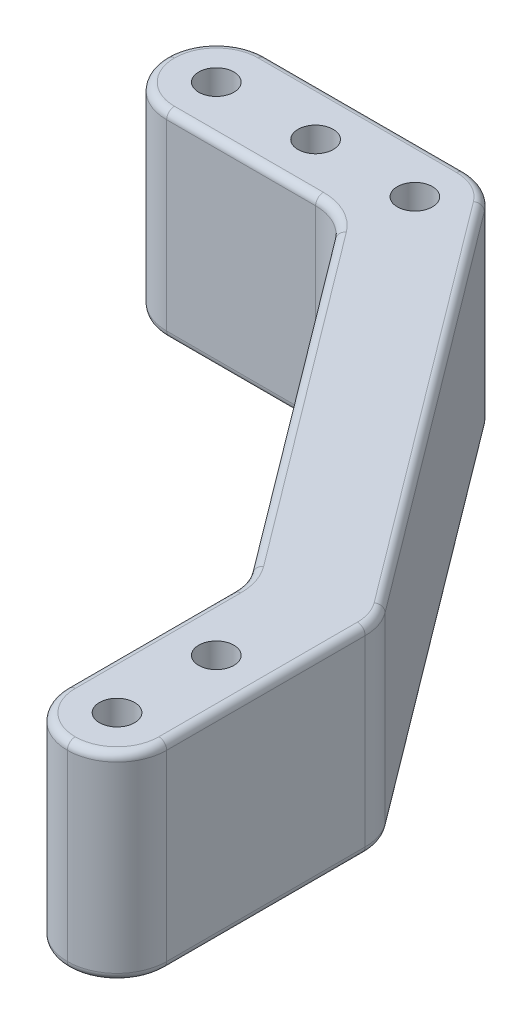
SolidWorks part; units mm, degrees
ref_plane "Front Plane" through (0, 0, 0) normal (0, 0, 1) x (1, 0, 0)
ref_plane "Top Plane" through (0, 0, 0) normal (0, 1, 0) x (1, 0, 0)
ref_plane "Right Plane" through (0, 0, 0) normal (1, 0, 0) x (0, 0, -1)
sketch "Sketch1" plane through (0, 0, 0) normal (0, 1, 0) x (1, 0, 0)
  line L0 (0, 0) -> (25.4, 0) construction
  line L1 (25.4, 0) -> (63.5, -50.8) construction
  line L2 (63.5, -50.8) -> (63.5, -76.2) construction
  line L3 (-6.35, 6.35) -> (-6.35, -6.35)
  line L4 (-6.35, -6.35) -> (22.225, -6.35)
  line L5 (22.225, -6.35) -> (57.15, -52.9167)
  line L6 (57.15, -52.9167) -> (57.15, -82.55)
  line L7 (57.15, -82.55) -> (69.85, -82.55)
  line L8 (69.85, -82.55) -> (69.85, -48.6833)
  line L9 (69.85, -48.6833) -> (28.575, 6.35)
  line L10 (28.575, 6.35) -> (-6.35, 6.35)
  circle A0 centre (0, 0) radius 2.25
  circle A1 centre (63.5, -76.2) radius 2.25
  circle A2 centre (63.5, -63.5) radius 2.25
  circle A3 centre (12.7, 0) radius 2.25
  circle A4 centre (25.4, 0) radius 2.25
  dimension "D10" = 4.5
  dimension "D1" = 25.4
  dimension "D2" = 25.4
  dimension "D3" = 50.8
  dimension "D4" = 38.1
  dimension "D5" = 12.7
  dimension "D6" = 12.7
  dimension "D7" = 6.35
  dimension "D8" = 6.35
  dimension "D9" = 12.7
  dimension "D11" = 3
extrude "Boss-Extrude1" add sketch "Sketch1" along normal blind 25.4
fillet "Fillet1" radius 6.35 8 edges at (28.575, 12.7, -6.35) (22.225, 12.7, 6.35) (69.85, 12.7, 48.6833) (57.15, 12.7, 52.9167) (69.85, 12.7, 82.55) (57.15, 12.7, 82.55) (-6.35, 12.7, -6.35) (-6.35, 12.7, 6.35)
fillet "Fillet2" radius 1 28 edges at (-4.4901, 0, 4.4901) (-4.4901, 0, -4.4901) (12.7, 0, -6.35) (28.2398, 0, -5.6796) (49.53, 0, 21.59) (69.5241, 0, 48.792) (69.85, 0, 63.5) (67.9901, 0, 80.6901) (59.0099, 0, 80.6901) (57.15, 0, 65.6167) (56.8241, 0, 53.0253) (40.005, 0, 30.0567) (21.8898, 0, 7.0204) (-4.4901, 25.4, 4.4901) (-4.4901, 25.4, -4.4901) (12.7, 25.4, -6.35) (28.2398, 25.4, -5.6796) (49.53, 25.4, 21.59) (69.5241, 25.4, 48.792) (69.85, 25.4, 63.5) (67.9901, 25.4, 80.6901) (59.0099, 25.4, 80.6901) (57.15, 25.4, 65.6167) (56.8241, 25.4, 53.0253) (40.005, 25.4, 30.0567) (21.8898, 25.4, 7.0204) (9.525, 0, 6.35) (9.525, 25.4, 6.35)
